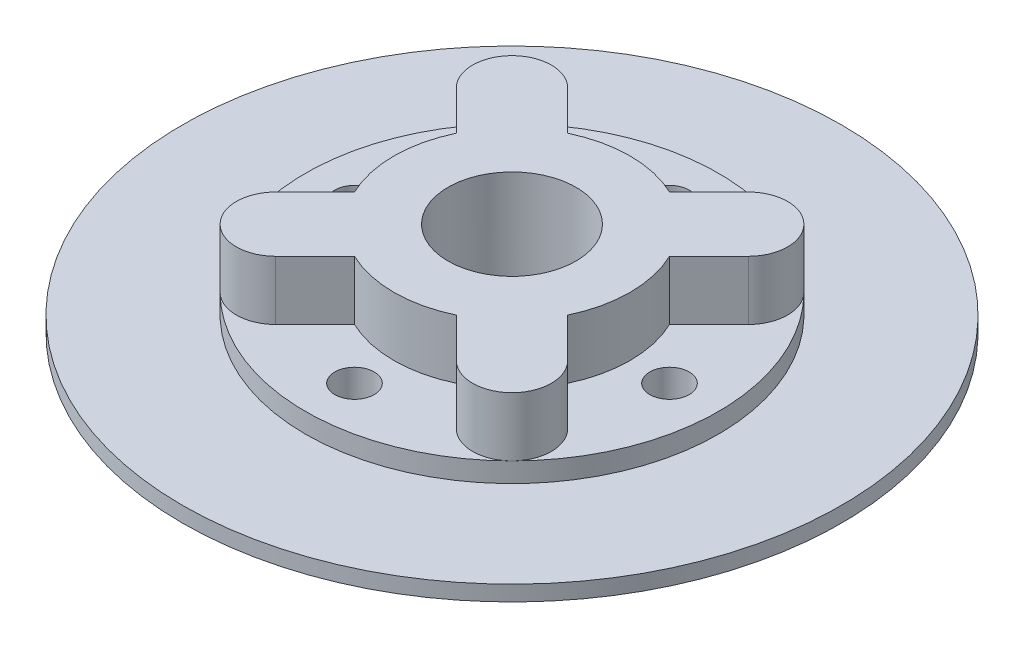
SolidWorks part; units mm, degrees
material "6061-T6 (SS)"
ref_plane "Front Plane" through (0, 0, 0) normal (0, 0, 1) x (1, 0, 0)
ref_plane "Top Plane" through (0, 0, 0) normal (0, 1, 0) x (1, 0, 0)
ref_plane "Right Plane" through (0, 0, 0) normal (1, 0, 0) x (0, 0, -1)
sketch "Sketch1" plane through (0, 0, 0) normal (0, 1, 0) x (1, 0, 0)
  circle A0 centre (0, 0) radius 53.1474
extrude "Boss-Extrude1" add sketch "Sketch1" along normal blind 2.4892
sketch "Sketch2" plane through (0, 2.4892, 0) normal (0, 1, 0) x (1, 0, 0)
  line L0 (-14.5599, 23.5401) -> (-8.2099, 17.1901)
  line L1 (-19.05, -19.05) -> (19.05, -19.05) construction
  line L2 (-19.05, -19.05) -> (-19.05, 19.05) construction
  line L3 (-19.05, 19.05) -> (19.05, 19.05) construction
  line L4 (19.05, -19.05) -> (19.05, 19.05) construction
  line L5 (-19.05, -19.05) -> (19.05, 19.05) construction
  line L6 (-19.05, 19.05) -> (19.05, -19.05) construction
  line L7 (-23.5401, 14.5599) -> (-17.1901, 8.2099)
  line L8 (23.5401, 14.5599) -> (17.1901, 8.2099)
  line L9 (14.5599, 23.5401) -> (8.2099, 17.1901)
  line L10 (14.5599, -23.5401) -> (8.2099, -17.1901)
  line L11 (23.5401, -14.5599) -> (17.1901, -8.2099)
  line L12 (-23.5401, -14.5599) -> (-17.1901, -8.2099)
  line L13 (-14.5599, -23.5401) -> (-8.2099, -17.1901)
  circle A0 centre (0, 0) radius 19.05
  circle A1 centre (-19.05, 19.05) radius 6.35
  circle A2 centre (19.05, 19.05) radius 6.35
  circle A3 centre (19.05, -19.05) radius 6.35
  circle A4 centre (-19.05, -19.05) radius 6.35
  point P33 (0, 0)
  dimension "D1" = 38.1
  dimension "D3" = 12.7
  dimension "D4" = 4
  dimension "D2" = 38.1
extrude "Boss-Extrude2" add sketch "Sketch2" along normal blind 12.7 contours A1 | A1 L7 A0 L0 | A0 | A2 | A2 L9 A0 L8 | A3 L11 A0 L10 | A3 | A4 | A4 L13 A0 L12 | A2 region at (-11.5382, 2.4892, -20.2118) region at (-19.05, 2.4892, -19.05) region at (0, 2.4892, 0) region at (11.5382, 2.4892, -20.2118) region at (19.05, 2.4892, -19.05) region at (-13.6237, 2.4892, 13.6237) region at (-19.05, 2.4892, 19.05) region at (20.2118, 2.4892, 11.5382) region at (19.05, 2.4892, 19.05)
sketch "Sketch3" plane through (0, 2.4892, 0) normal (0, 1, 0) x (1, 0, 0)
  circle A0 centre (0, 0) radius 33.2908
extrude "Boss-Extrude3" add sketch "Sketch3" along normal blind 3.175
sketch "Sketch4" plane through (0, 15.1892, 0) normal (0, 1, 0) x (1, 0, 0)
  circle A0 centre (0, 0) radius 10.3187
  dimension "D1" = 20.6375
extrude "Cut-Extrude1" cut sketch "Sketch4" against normal through all
sketch "Sketch5" plane through (0, 0, 0) normal (0, -1, 0) x (1, 0, 0)
  circle A0 centre (0, 0) radius 10.3187
  arc A1 (-23.5401, 23.5401) -> (-23.5401, -23.5401) centre (0, 0) ccw construction
  arc A2 (-23.5401, 23.5401) -> (-23.5401, -23.5401) centre (0, 0) ccw
  circle A3 centre (0, 0) radius 33.2908
  circle M1 centre (0, 0) radius 10.3187
extrude "Boss-Extrude4" add sketch "Sketch5" along normal blind 3.175 contours A2 A3 M1 region at (12.3795, 0, 29.8867)
sketch "Sketch6" plane through (0, 5.6642, 0) normal (0, 1, 0) x (1, 0, 0)
  circle A0 centre (0, 25.4) radius 3.175
  arc A1 (23.5401, 23.5401) -> (-23.5401, 23.5401) centre (0, 0) ccw construction
  circle A2 centre (25.4, 0) radius 3.175
  circle A3 centre (0, -25.4) radius 3.175
  circle A4 centre (-25.4, 0) radius 3.175
  arc A5 (8.2099, 17.1901) -> (-8.2099, 17.1901) centre (0, 0) ccw construction
  point P2 (0, 19.05)
  point P3 (0, 33.2908)
  point P4 (0, 0)
  point P16 (0, 0)
  point P19 (0, 0)
  dimension "D1" = 6.35
  dimension "D2" = 6.35
  dimension "D3" = 4
extrude "Cut-Extrude2" cut sketch "Sketch6" against normal through all
